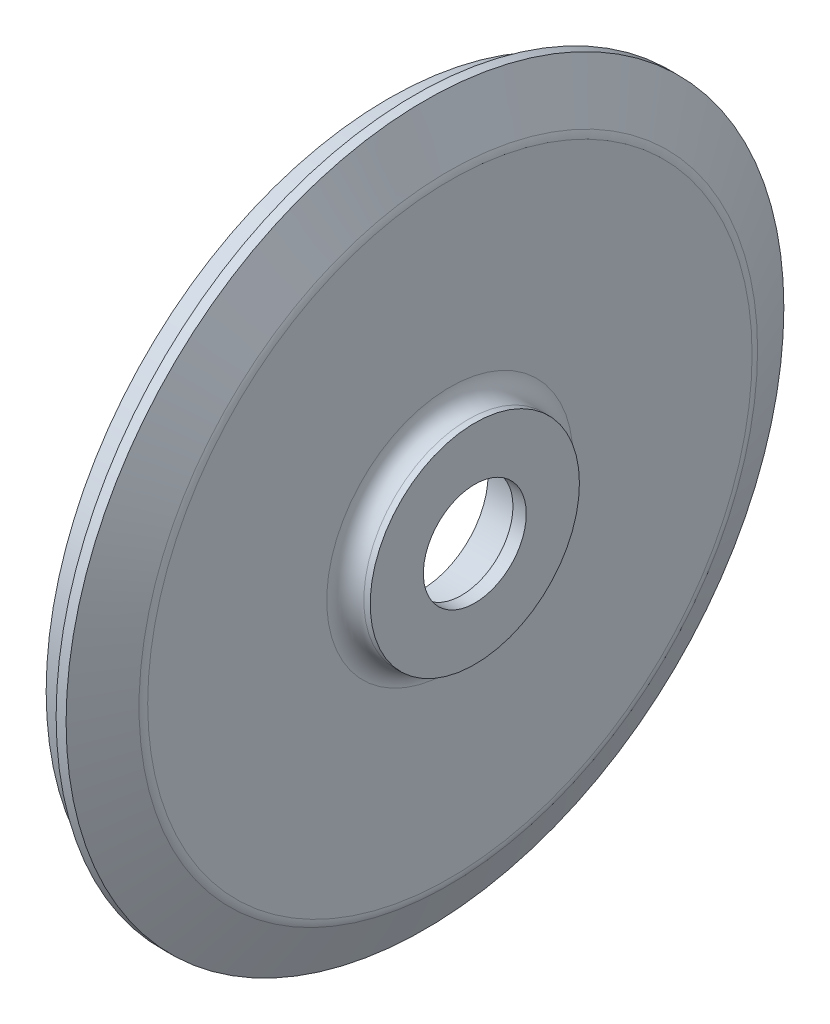
SolidWorks part; units mm, degrees
material "6061 Alloy"
ref_plane "Front Plane" through (0, 0, 0) normal (0, 0, 1) x (1, 0, 0)
ref_plane "Top Plane" through (0, 0, 0) normal (0, 1, 0) x (1, 0, 0)
ref_plane "Right Plane" through (0, 0, 0) normal (1, 0, 0) x (0, 0, -1)
sketch "Sketch1" plane through (0, 0, 0) normal (0, 0, 1) x (1, 0, 0)
  line L0 (0, 0) -> (-41.2566, 0) construction
  line L1 (-3.2523, 15.4808) -> (-7.2523, 15.4808)
  line L2 (-7.2523, 15.4808) -> (-7.2523, 20)
  line L3 (-7.2523, 20) -> (-26.2523, 20) construction
  line L4 (-26.2523, 20) -> (-26.2523, 100) construction
  line L5 (-26.2523, 100) -> (-29.2523, 100)
  line L6 (-29.2523, 100) -> (-29.2523, 103)
  line L7 (-29.2523, 103) -> (-3.2523, 103) construction
  line L8 (-3.2523, 103) -> (-3.2523, 15.4808) construction
  line L11 (-3.2523, 103) -> (-3.2523, 108) construction
  line L12 (-3.2523, 108) -> (-21.2523, 108) construction
  line L13 (-21.2523, 108) -> (-21.2523, 103)
  line L14 (-21.2523, 103) -> (-29.2523, 103)
  line L15 (-26.2523, 100) -> (-26.2523, 92.0483)
  line L16 (-26.2523, 92.0483) -> (-24.2523, 92.0483)
  line L17 (-19.2523, 87.0483) -> (-19.2523, 20)
  line L18 (-19.2523, 20) -> (-7.2523, 20)
  line L19 (-3.2523, 15.4808) -> (-3.2523, 31.4808)
  line L20 (-3.2523, 31.4808) -> (-5.1725, 31.4808)
  line L21 (-21.2523, 108) -> (-18.2523, 108)
  line L23 (-26.2523, -100) -> (-26.2523, 100) construction
  line L25 (-10.7523, 90.943) -> (-10.7523, 37.0606)
  line L26 (-18.2523, 108) -> (-11.2281, 93.0718)
  arc A0 (-10.7523, 37.0606) -> (-5.1725, 31.4808) centre (-5.1725, 37.0606) ccw
  arc A2 (-19.2523, 87.0483) -> (-24.2523, 92.0483) centre (-24.2523, 87.0483) ccw
  arc A3 (-10.7523, 90.943) -> (-11.2281, 93.0718) centre (-15.7523, 90.943) ccw
  point P2 (-7.2523, 15.4808)
  point P12 (-26.2523, 90.0483)
  point P26 (-19.629, 108)
  point P27 (-23.2523, 108)
  point P35 (-10.7523, 92.0606)
  point P38 (-18.2523, 108)
  point P39 (-10.7523, 90.3339)
  point P40 (0, 0)
  point P41 (-21.7509, 106.0855)
  point P42 (-11.8179, 93.4193)
  point P43 (-10.7523, 92.0483)
  point P44 (-10.7523, 90.3339)
  point P45 (-5.1725, 31.4808)
  point P46 (-10.7523, 37.0606)
  point P47 (-3.2523, 31.4808)
  point P48 (-3.2523, 103)
  point P49 (-3.2523, 108)
  point P50 (-26.2523, 108)
  point P51 (-11.8179, 93.4193)
  point P52 (-10.7523, 90.3339)
  point P53 (-10.7523, 90.3339)
  point P54 (-3.2523, 31.4808)
  point P55 (-5.1725, 31.4808)
  point P56 (-10.7523, 37.0606)
  point P57 (-11.8179, 93.4193)
  point P58 (-10.7523, 92.0483)
  point P59 (-17.3985, 106.1853)
  point P60 (0, 0)
  point P61 (-18.2523, 108)
  point P62 (-18.3264, 108)
  dimension "D10" = 5.5798
  dimension "D14" = 5
  dimension "D1" = 20
  dimension "D2" = 12
  dimension "D3" = 3
  dimension "D4" = 3
  dimension "D5" = 5
  dimension "D6" = 100
  dimension "D7" = 4
  dimension "D8" = 2
  dimension "D9" = 3
  dimension "D11" = 8.5
  dimension "D12" = 16
  dimension "D13" = 55
  dimension "D15" = 5
revolve "Revolve1" add sketch "Sketch1" angle 360 about L0
